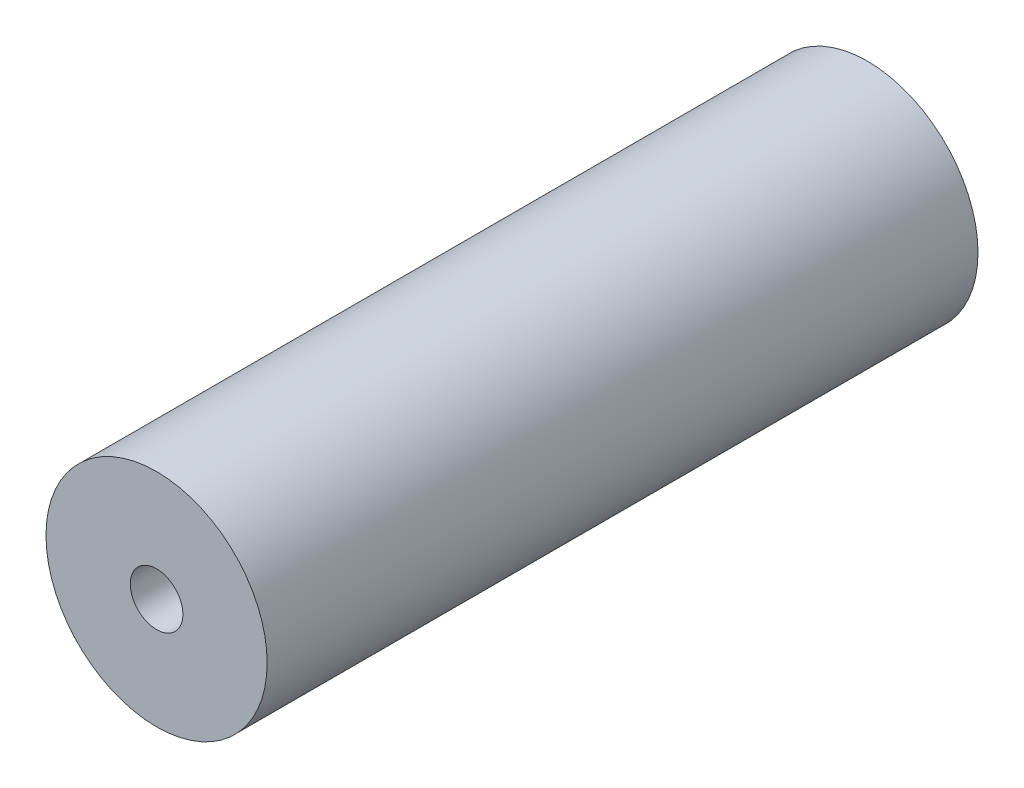
SolidWorks part; units mm, degrees
material "Cast Alloy Steel"
ref_plane "Front Plane" through (0, 0, 0) normal (0, 0, 1) x (1, 0, 0)
ref_plane "Top Plane" through (0, 0, 0) normal (0, 1, 0) x (1, 0, 0)
ref_plane "Right Plane" through (0, 0, 0) normal (1, 0, 0) x (0, 0, -1)
sketch "Sketch2" plane through (0, 0, 0) normal (0, 0, 1) x (1, 0, 0)
  circle A0 centre (0, 0) radius 21
extrude "Boss-Extrude1" add sketch "Sketch2" along normal blind 67.5 and the other way blind 67.5
sketch "Sketch3" plane through (0, 0, 67.5) normal (0, 0, 1) x (1, 0, 0)
  circle A0 centre (0, 0) radius 5
  dimension "D1" = 0
extrude "Cut-Extrude1" cut sketch "Sketch3" against normal blind 135
sketch "Sketch4" plane through (0, 0, -67.5) normal (0, 0, -1) x (-1, 0, 0)
  line L0 (0, 35.8542) -> (0, -31.7202) construction
  line L1 (-38.0006, 0) -> (55.6495, 0) construction
  circle A0 centre (0, 0) radius 17.5 construction
  circle A1 centre (0, 17.5) radius 2
  circle A2 centre (17.5, 0) radius 2
  circle A3 centre (0, -17.5) radius 2
  circle A4 centre (-17.5, 0) radius 2
extrude "Cut-Extrude2" cut sketch "Sketch4" against normal blind 9
